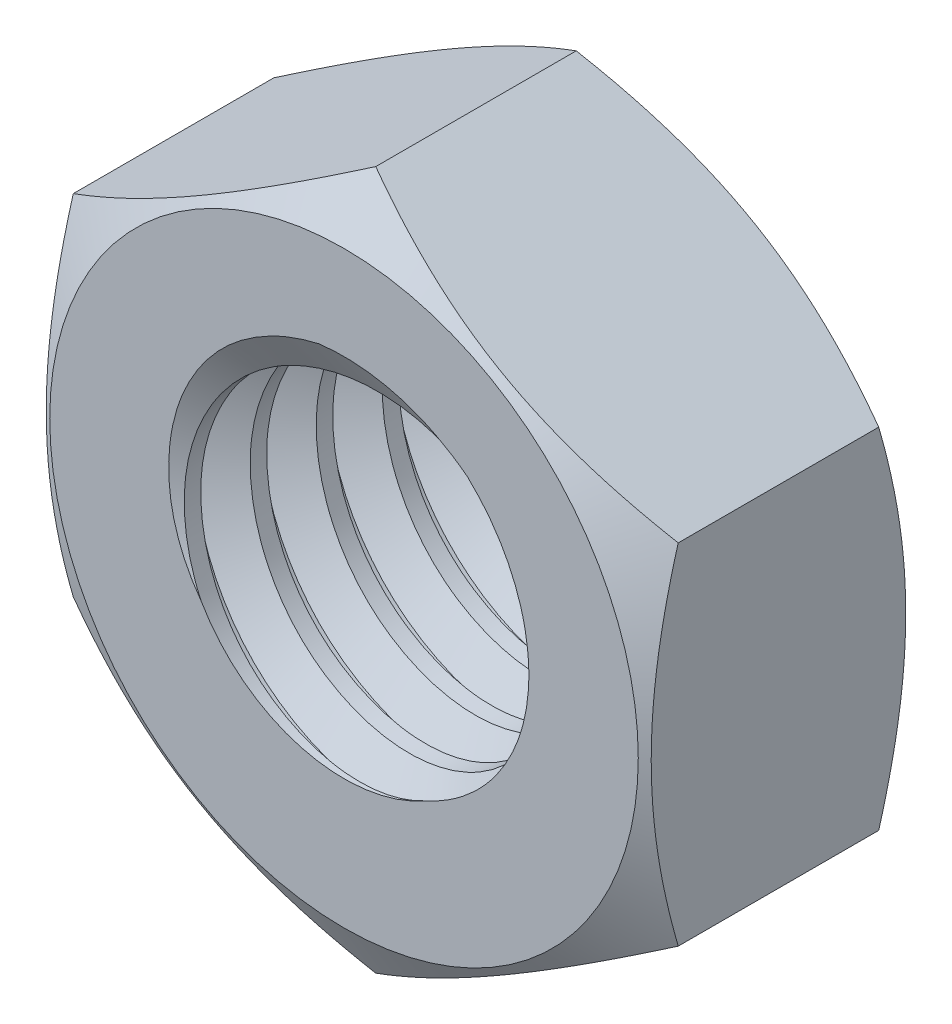
SolidWorks part; units mm, degrees
material "Hierro dúctil"
ref_plane "Alzado" through (0, 0, 0) normal (0, 0, 1) x (1, 0, 0)
ref_plane "Planta" through (0, 0, 0) normal (0, 1, 0) x (1, 0, 0)
ref_plane "Vista lateral" through (0, 0, 0) normal (1, 0, 0) x (0, 0, -1)
sketch "Croquis1" plane through (0, 0, 0) normal (0, 0, 1) x (1, 0, 0)
  line L1 (0, 3.1754) -> (-2.75, 1.5877)
  line L2 (-2.75, 1.5877) -> (-2.75, -1.5877)
  line L3 (-2.75, -1.5877) -> (0, -3.1754)
  line L4 (0, -3.1754) -> (2.75, -1.5877)
  line L5 (2.75, -1.5877) -> (2.75, 1.5877)
  line L6 (2.75, 1.5877) -> (0, 3.1754)
  circle A0 centre (0, 0) radius 2.75 construction
  circle A1 centre (0, 0) radius 1.5
  dimension "D1" = 5.5
  dimension "D2" = 3
extrude "Saliente-Extruir1" add sketch "Croquis1" along normal mid plane 2.4
sketch "Croquis2" plane through (0, 0, 0) normal (1, 0, 0) x (0, 0, -1)
  line L0 (0.9113, 3.1754) -> (1.2, 2.6754)
  line L1 (-1.2, 3.1754) -> (1.2, 3.1754) construction
  line L2 (1.2, 1.5877) -> (1.2, 3.1754) construction
  line L3 (1.2, 2.6754) -> (1.2, 3.1754)
  line L4 (1.2, 3.1754) -> (0.9113, 3.1754)
  line L5 (-1.2, 0) -> (1.2, 0) construction
  line L6 (-1.2, -1.5877) -> (-1.2, 1.5877) construction
  line L7 (1.2, -1.5877) -> (1.2, 1.5877) construction
  dimension "D1" = 30
  dimension "D2" = 0.5
revolve "Cortar-Revolución1" cut sketch "Croquis2" angle 360 about L5
mirror "Simetría1" about plane through (0, 0, 0) normal (0, 0, 1) of "Cortar-Revolución1"
thread "Rosca1" pitch 0.6 method cut profile "Perfil de rosca3" start angle 0, offset 1, length 4, pitch 0.6, diameter 3
ref_plane "Plano3" through (-1.5, 0, 2.2) normal (0, -1, 0) x (-1, 0, 0)
sketch "Perfil de rosca3" plane through (-1.5, 0, 2.2) normal (0, -1, 0) x (-1, 0, 0)
  line L0 (0, 0) -> (0, 0.6) construction
  line L1 (0, 0) -> (0.3248, 0.1875)
  line L2 (0.3248, 0.1875) -> (0.3248, 0.2625)
  line L3 (0.3248, 0.2625) -> (0, 0.45)
  line L4 (0.3248, 0.225) -> (0, 0.225) construction
  line L11 (0, 0) -> (0, 0.45)
  point P2 (0, 0)
  dimension "Pitch" = 0.6
  dimension "Profile_Angle" = 60
  dimension "Profile_Land" = 0.075
  dimension "Profile_Height" = 0.3248
